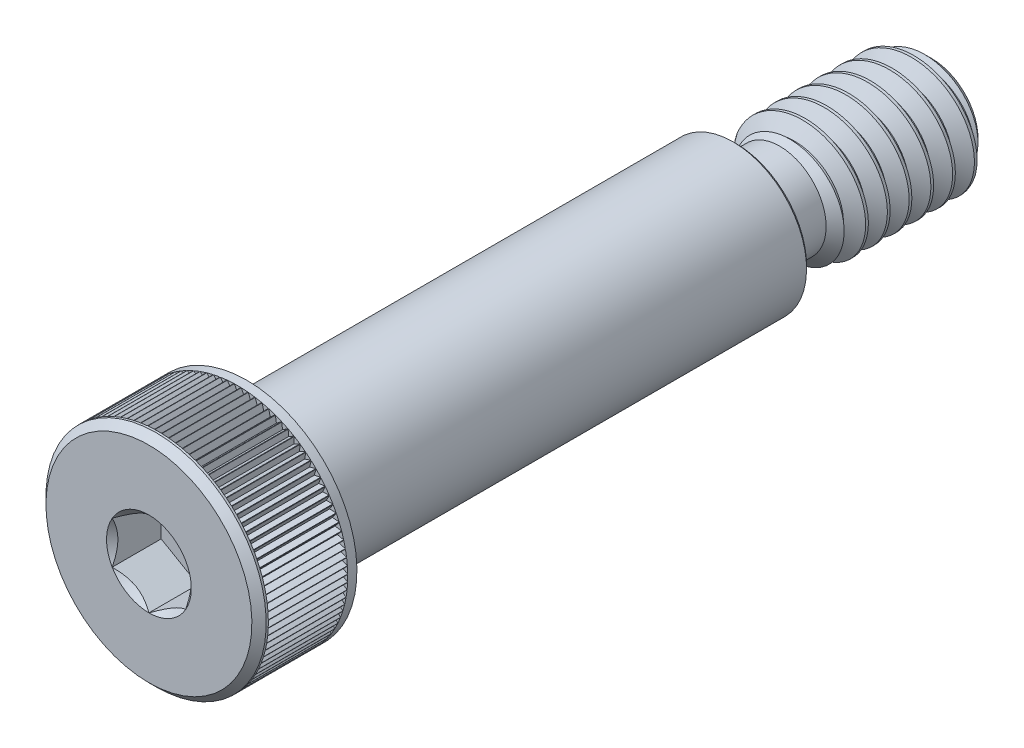
SolidWorks part; units mm, degrees
note: '?' marks a value the reader was unsure of.
material "Alloy Steel"
ref_plane "Front" through (0, 0, 0) normal (0, 0, 1) x (1, 0, 0)
ref_plane "Top" through (0, 0, 0) normal (0, 1, 0) x (1, 0, 0)
ref_plane "Right" through (0, 0, 0) normal (1, 0, 0) x (0, 0, -1)
sketch "Sketch1" plane through (0, 0, 0) normal (1, 0, 0) x (0, 0, -1)
  line L0 (0, 7.1437) -> (6.35, 7.1437)
  line L1 (6.35, 7.1437) -> (6.35, 4.7625)
  line L2 (6.35, 4.7625) -> (38.1, 4.7625)
  line L3 (38.1, 4.7625) -> (38.1, 3.9751)
  line L4 (38.1, 3.9751) -> (50.8, 3.9751)
  line L5 (50.8, 3.9751) -> (50.8, 0)
  line L6 (50.8, 0) -> (0, 0)
  line L7 (0, 0) -> (0, 7.1437)
  line L8 (0, 7.1437) -> (0, -7.1438) construction
  line L9 (50.8, 3.9751) -> (50.8, -3.9751) construction
  line L10 (38.1, 4.7625) -> (38.1, -4.7625) construction
  line L11 (50.8, -3.9751) -> (49.1222, -3.9751) construction
  line L12 (22.225, 0) -> (22.225, 4.7625) construction
  point P8 (48.6833, -3.9751)
  point P12 (38.1, 0)
  point P17 (9.525, 4.7625)
  point P18 (22.225, 0)
  point P19 (22.225, 4.7625)
  point P20 (34.925, 4.7625)
  point P21 (34.925, -4.7625)
  point P22 (9.525, -4.7625)
  dimension "Head Dia" = 14.2875
  dimension "Head Ht" = 6.35
  dimension "Thread Lg" = 12.7
  dimension "Thread Dia" = 7.9502
  dimension "Shoulder Dia" = 9.525
  dimension "Shoulder Lg" = 31.75
  dimension "D1" = 2.1167
  dimension "D2" = 1.6778
  dimension "D3" = 15.875
  dimension "D4" = 3.175
revolve "Revolve1" add sketch "Sketch1" angle 360 mid plane about L6
ref_plane "Plane1" through (0, 0, -50.8) normal (0, 0, 1) x (1, 0, 0)
sketch "Sketch3" plane through (0, 0, -50.8) normal (0, 0, 1) x (1, 0, 0)
  circle A0 centre (0, 0) radius 3.9751
sketch "Sketch5" plane through (0, 0, 0) normal (1, 0, 0) x (0, 0, -1)
  line L0 (38.1, 4.7625) -> (42.672, 4.7625)
  line L1 (42.672, 4.7625) -> (40.9194, 3.0099)
  line L2 (40.9194, 3.0099) -> (39.0652, 3.0099)
  line L3 (38.1, 4.7625) -> (38.1, 3.9751)
  line L5 (38.1, 3.9751) -> (50.8, 3.9751) construction
  line L6 (50.8, 0) -> (40.9194, 0) construction
  line L7 (45.8597, 0) -> (45.8597, -3.9751) construction
  arc A0 (38.1, 3.9751) -> (39.0652, 3.0099) centre (39.0652, 3.9751) ccw
  dimension "D1" = 45
  dimension "CADB" = 2.8194
  dimension "CADA" = 6.0198
revolve "Cut-Revolve1" cut sketch "Sketch5" angle 360 mid plane about L6
chamfer "Chamfer1" distance 0.9938 angle 45 1 edges at (0, 3.9751, -50.8)
chamfer "Chamfer2" distance 0.4643 angle 45 1 edges at (0, 7.1437, 0)
chamfer "Chamfer3" distance 0.2032 angle 45 1 edges at (0, 4.7625, -38.1)
sketch "Sketch10" plane through (0, 0, 0) normal (1, 0, 0) x (0, 0, -1)
  line L0 (0.4643, 0) -> (5.8857, 0) construction
  line L1 (0.4643, -7.1437) -> (0.4643, 7.1437) construction
  line L3 (0.4643, 0) -> (0, 0) construction
  line L4 (5.8857, 0) -> (6.35, 0) construction
  line L5 (6.35, -7.1438) -> (6.35, 7.1437) construction
  point P6 (3.175, 0)
  dimension "D1" = 5.4213
ref_plane "Plane2" through (0, 0, -3.175) normal (0, 0, 1) x (1, 0, 0)
sketch "Sketch11" plane through (0, 0, -3.175) normal (0, 0, 1) x (1, 0, 0)
  line L0 (0, 6.7723) -> (0, 7.1437) construction
  line L1 (0, 6.7723) -> (0.2145, 7.1437)
  line L2 (0, 6.7723) -> (-0.2145, 7.1437)
  line L3 (-0.2145, 7.1437) -> (0.2145, 7.1437)
  line L4 (0, 0) -> (-0.2145, 7.1437) construction
  line L5 (0.2145, 7.1437) -> (0, 0) construction
  circle A1 centre (0, 0) radius 7.1437 construction
  circle A2 centre (0, 0) radius 6.7723 construction
  circle A3 centre (0, 0) radius 6.6794 construction
  point P3 (0, 0.0018)
  point P8 (2.3908, 0.7309)
  dimension "D1" = 0.3715
  dimension "D2" = 3.439
extrude "Cut-Extrude5" cut sketch "Sketch11" against normal mid plane 5.1502
pattern_circular "CirPattern1" count 99 over 360 about axis through (0, 0, 0) along (0, 0, 1) of "Cut-Extrude5"
sketch "Sketch8" plane through (0, 0, 0) normal (0, 0, 1) x (1, 0, 0)
  line L1 (2.3813, 1.3748) -> (0, 2.7496)
  line L2 (0, 2.7496) -> (-2.3812, 1.3748)
  line L3 (-2.3812, 1.3748) -> (-2.3812, -1.3748)
  line L4 (-2.3812, -1.3748) -> (0, -2.7496)
  line L5 (0, -2.7496) -> (2.3813, -1.3748)
  line L6 (2.3813, -1.3748) -> (2.3813, 1.3748)
  circle A0 centre (0, 0) radius 2.3812 construction
  dimension "Hex" = 4.7625
extrude "Cut-Extrude2" cut sketch "Sketch8" against normal blind 3.175
sketch "Sketch9" plane through (0, 0, 0) normal (0, 0, 1) x (1, 0, 0)
  circle A0 centre (0, 0) radius 2.7496
extrude "Cut-Extrude4" cut sketch "Sketch9" against normal blind 3.175 draft 45
sketch "Front Sketch" plane through (0, 0, 0) normal (0, 0, 1) x (1, 0, 0)
  line L0 (2.3813, -1.3748) -> (2.3813, 1.3748) construction
  line L1 (-2.3812, 1.3748) -> (-2.3812, -1.3748) construction
  circle A0 centre (0, 0) radius 7.1437 construction
  point P4 (-2.3812, 0)
  point P5 (2.3813, 0)
  point P6 (7.1437, 0)
  point P9 (-7.1437, 0)
ref_plane "Contact Plane 1" through (0, 0, -6.35) normal (0, 0, -1) x (-1, 0, 0)
ref_axis "Center Axis 1" through (0, 0, -50.8) along (0, 0, 1)?
curve "Helix/Spiral1" pitch 1.4111 height 14.1111 turns 10
sketch "Sketch4" plane through (0, 0, 0) normal (1, 0, 0) x (0, 0, -1)
  line L0 (50.7118, 4.1279) -> (52.1229, 4.1279) construction
  line L1 (52.1229, 4.1279) -> (51.4174, 2.9058) construction
  line L3 (51.4174, 2.9058) -> (50.7118, 4.1279) construction
  line L4 (50.7559, 4.0515) -> (52.0788, 4.0515) construction
  line L5 (50.8, 3.9751) -> (52.0347, 3.9751) construction
  line L6 (51.3292, 3.0586) -> (51.5056, 3.0586) construction
  line L7 (51.4174, 3.0586) -> (51.4174, 2.9058) construction
  line L8 (51.4174, 4.1279) -> (51.4174, 3.9751) construction
  line L9 (50.7559, 4.0515) -> (52.0788, 4.0515)
  line L10 (52.0788, 4.0515) -> (51.5056, 3.0586)
  line L11 (51.5056, 3.0586) -> (51.3292, 3.0586)
  line L12 (51.3292, 3.0586) -> (50.7559, 4.0515)
  point P14 (51.4174, 4.0515)
  point P15 (51.4174, 4.1279)
  dimension "D1" = 1.4111
  dimension "D2" = 0.1764
sweep "Cut-Sweep1" cut profiles "Sketch4" path "Helix/Spiral1" align with end faces yes
sketch "Sketch12" plane through (0, 0, 0) normal (1, 0, 0) x (0, 0, -1)
  line L1 (38.1, 4.5593) -> (37.8968, 4.7625)
  line L2 (37.8968, 4.7625) -> (6.35, 4.7625)
  line L3 (6.35, 4.7625) -> (6.35, 0)
  line L4 (6.35, -7.1438) -> (6.35, 7.1437) construction
  line L5 (6.35, 0) -> (38.1, 0)
  line L6 (38.1, 4.5593) -> (38.1, 3.9751)
  line L7 (40.9194, 3.0099) -> (39.0652, 3.0099) construction
  line L8 (40.9194, 3.0099) -> (39.0652, 3.0099)
  line L9 (40.9194, 3.0099) -> (40.9194, 0)
  line L10 (40.9194, 0) -> (38.1, 0)
  arc A0 (38.1, 3.9751) -> (39.0652, 3.0099) centre (39.0652, 3.9751) ccw construction
  arc A1 (38.1, 3.9751) -> (39.0652, 3.0099) centre (39.0652, 3.9751) ccw
revolve "Revolve2" add sketch "Sketch12" angle 360 about L5
equation "\"D3@Helix/Spiral1\" = \"Thread Lg@Sketch1\" + \"D4@Helix/Spiral1\""
equation "\"D1@Chamfer1\" = \"Thread Dia@Sketch1\" * .125"
equation "\"D1@Cut-Extrude2\"= \"Head Ht@Sketch1\" * .5"
equation "\"D1@Cut-Extrude4\" = \"D1@Cut-Extrude2\""
equation "\"D1@Chamfer2\" = \"Head Dia@Sketch1\" * .0325"
equation "\"D1@Sketch1\"=\"D4@Helix/Spiral1\"*1.5"
equation "\"D1@Sketch11\"=\"D1@Chamfer2\"*.8"
equation "\"D1@Cut-Extrude5\"=\"D1@Sketch10\"*.95"
equation "\"D1@CirPattern1\"=(360/\"D2@Sketch11\")-6"
equation "\"D3@Sketch1\"=\"Shoulder Lg@Sketch1\"/2"
equation "\"D4@Sketch1\"=\"D3@Sketch1\"*.2"
equation "\"D1@Sketch4\"=\"D4@Helix/Spiral1\""
equation "\"D2@Sketch4\"=\"D1@Sketch4\"/8"
